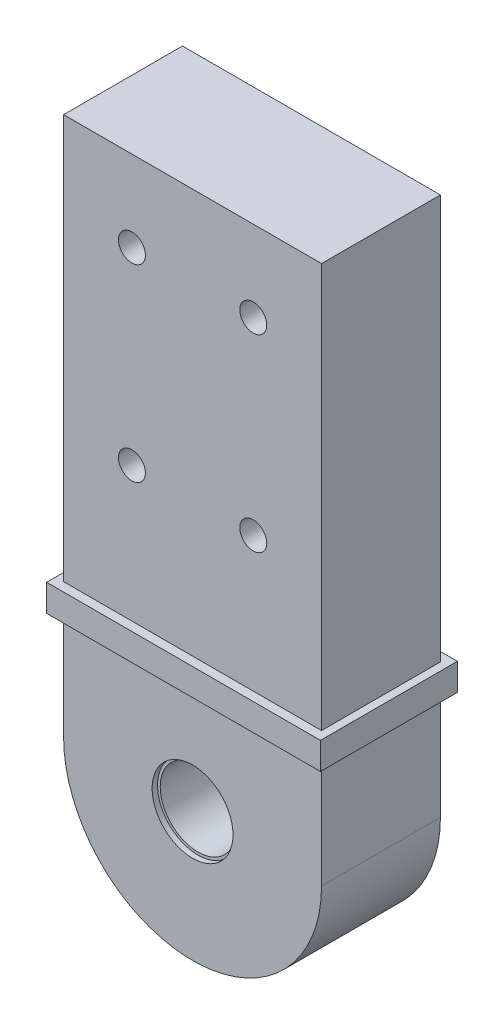
SolidWorks part; units mm, degrees
ref_plane "Front Plane" through (0, 0, 0) normal (0, 0, 1) x (1, 0, 0)
ref_plane "Top Plane" through (0, 0, 0) normal (0, 1, 0) x (1, 0, 0)
ref_plane "Right Plane" through (0, 0, 0) normal (1, 0, 0) x (0, 0, -1)
sketch "Sketch1" plane through (0, 0, 0) normal (0, 0, 1) x (1, 0, 0)
  line L0 (-23.925, 0) -> (-23.925, 100)
  line L1 (-23.925, 100) -> (23.925, 100)
  line L2 (23.925, 100) -> (23.925, 0)
  line L4 (-11.25, 85) -> (11.25, 85) construction
  line L5 (-11.25, 85) -> (-11.25, 50) construction
  line L6 (-11.25, 50) -> (11.25, 50) construction
  line L7 (11.25, 85) -> (11.25, 50) construction
  circle A0 centre (0, 0) radius 7
  arc A1 (-23.925, 0) -> (23.925, 0) centre (0, 0) ccw
  circle A2 centre (-11.25, 85) radius 2.5
  circle A3 centre (11.25, 85) radius 2.5
  circle A4 centre (11.25, 50) radius 2.5
  circle A5 centre (-11.25, 50) radius 2.5
  point P13 (0, 50)
  dimension "D1" = 14
  dimension "D4" = 5
  dimension "D2" = 47.85
  dimension "D3" = 100
  dimension "D5" = 35
  dimension "D6" = 15
  dimension "D7" = 22.5
extrude "Boss-Extrude1" add sketch "Sketch1" along normal blind 22.05
sketch "Sketch2" plane through (0, 0, 22.05) normal (0, 0, 1) x (1, 0, 0)
  circle A0 centre (0, 0) radius 7.5
  dimension "D1" = 15
extrude "Cut-Extrude1" cut sketch "Sketch2" against normal blind 1
sketch "Sketch3" plane through (0, 0, 0) normal (0, 0, -1) x (-1, 0, 0)
  circle A0 centre (0, 0) radius 7.5
  dimension "D1" = 15
extrude "Cut-Extrude2" cut sketch "Sketch3" against normal blind 1
sketch "Sketch4" plane through (0, 0, 22.05) normal (0, 0, 1) x (1, 0, 0)
  line L0 (-23.925, 24.981) -> (23.925, 24.981)
  line L1 (-23.925, 100) -> (-23.925, 0) construction
  line L2 (23.925, 0) -> (23.925, 100) construction
  circle A0 centre (11.25, 50) radius 2.5
  circle A1 centre (11.25, 50) radius 2.5 construction
  dimension "D1" = 25.019
ref_plane "Plane1" through (0, 24.981, 0) normal (0, 1, 0) x (1, 0, 0)
sketch "Sketch5" plane through (0, 24.981, 0) normal (0, 1, 0) x (1, 0, 0)
  line L4 (23.925, 0) -> (-23.925, 0)
  line L5 (-23.925, 0) -> (-23.925, -22.05)
  line L6 (-23.925, -22.05) -> (23.925, -22.05)
  line L7 (23.925, -22.05) -> (23.925, 0)
  line L8 (23.925, 0) -> (-23.925, 0)
  line L9 (-23.925, 0) -> (-23.925, -22.05)
  line L10 (-23.925, -22.05) -> (23.925, -22.05)
  line L11 (23.925, -22.05) -> (23.925, 0)
  line L20 (25.4, 1.675) -> (-25.4, 1.675)
  line L21 (-25.4, 1.675) -> (-25.4, -23.725)
  line L22 (-25.4, -23.725) -> (25.4, -23.725)
  line L23 (25.4, -23.725) -> (25.4, 1.675)
  point P2 (-25.4, -11.025)
  point P4 (-23.925, -11.025)
  point P6 (0, 1.675)
  dimension "D3" = 50.8
  dimension "D2" = 25.4
  dimension "D1" = 0
extrude "Boss-Extrude2" add sketch "Sketch5" against normal blind 5
